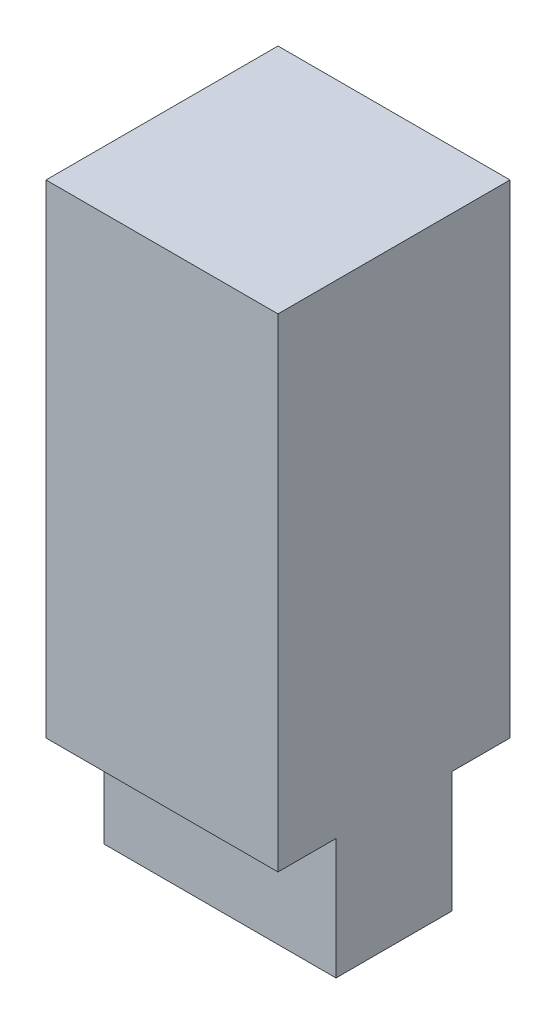
SolidWorks part; units mm, degrees
ref_plane "Front Plane" through (0, 0, 0) normal (0, 0, 1) x (1, 0, 0)
ref_plane "Top Plane" through (0, 0, 0) normal (0, 1, 0) x (1, 0, 0)
ref_plane "Right Plane" through (0, 0, 0) normal (1, 0, 0) x (0, 0, -1)
sketch "Sketch2" plane through (0, 0, 0) normal (1, 0, 0) x (0, 0, -1)
  line L0 (0, 0) -> (-1.524, 0)
  line L1 (-1.524, 0) -> (-1.524, 3.175)
  line L2 (-1.524, 3.175) -> (-3.048, 3.175)
  line L3 (-3.048, 3.175) -> (-3.048, 15.875)
  line L4 (-3.048, 15.875) -> (3.048, 15.875)
  line L5 (3.048, 15.875) -> (3.048, 3.175)
  line L6 (3.048, 3.175) -> (1.524, 3.175)
  line L7 (1.524, 3.175) -> (1.524, 0)
  line L8 (1.524, 0) -> (0, 0)
  dimension "D1" = 3.048
  dimension "D2" = 3.175
  dimension "D3" = 12.7
  dimension "D4" = 1.524
extrude "Boss-Extrude1" add sketch "Sketch2" along normal blind 6.096
